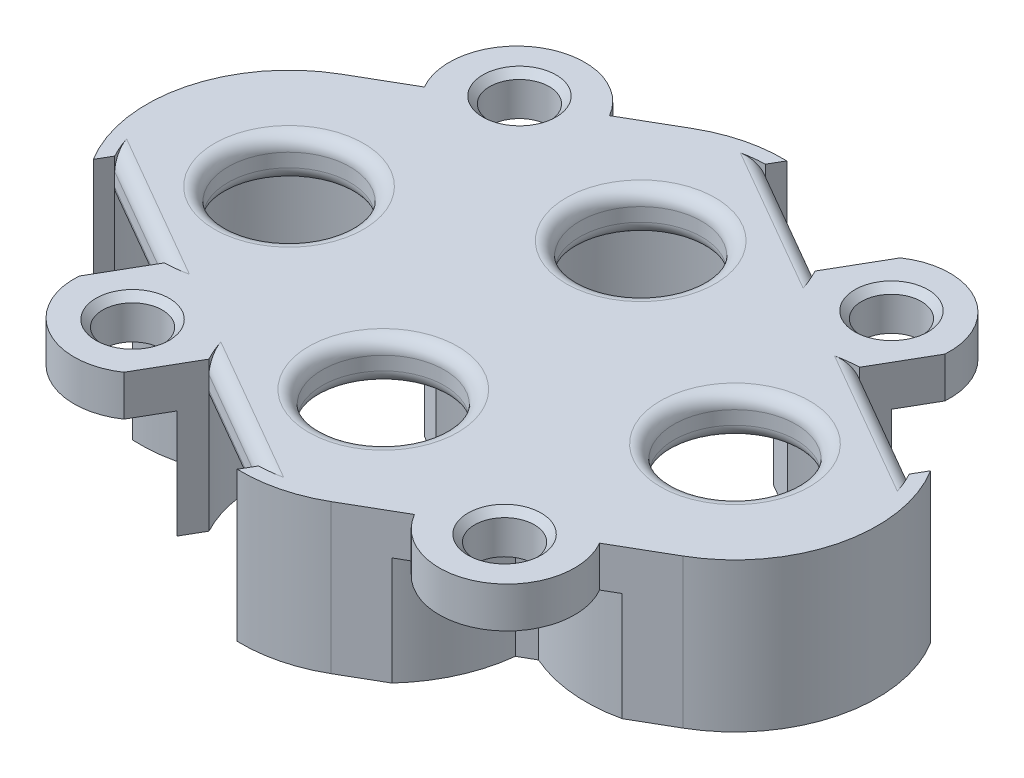
SolidWorks part; units mm, degrees
note: The reader was unsure of these and kept them because the rebuilt part matched: shared geometry of "Sketch1<4>", "Sketch1<6>".
ref_plane "Front Plane" through (0, 0, 0) normal (0, 0, 1) x (1, 0, 0)
ref_plane "Top Plane" through (0, 0, 0) normal (0, 1, 0) x (1, 0, 0)
ref_plane "Right Plane" through (0, 0, 0) normal (1, 0, 0) x (0, 0, -1)
sketch "Sketch1" plane through (0, 0, 0) normal (0, 1, 0) x (1, 0, 0)
  line L0 (-11.9589, 8.369) -> (-9.4955, 9.7913)
  line L1 (-6.9589, -0.2913) -> (-4.4955, 1.131)
  line L2 (-16.4545, 0) -> (0, 9.5) construction
  line L3 (-12.0193, 10.0662) -> (-10.9352, 10.6921)
  line L4 (0, 9.0625) -> (0, -9.0625) construction
  line L5 (-16.4545, 0) -> (16.4545, 0) construction
  line L6 (-5.25, 18.5933) -> (-21.7045, 9.0933)
  line L7 (5.25, -18.5933) -> (21.7045, -9.0933)
  line L8 (-21.7045, -9.0933) -> (-5.25, -18.5933)
  line L9 (5.25, 18.5933) -> (21.7045, 9.0933)
  line L10 (-12.0193, -10.0662) -> (-10.9352, -10.6921)
  line L11 (-16.4545, 0) -> (0, -9.5) construction
  line L12 (0, -19) -> (0, -20)
  line L13 (0, 20) -> (0, 19)
  line L14 (-11.9589, -8.369) -> (-9.4955, -9.7913)
  line L15 (0, 0) -> (-27.9836, 16.1563) construction
  circle A0 centre (-16.4545, 0) radius 9.5
  circle A1 centre (0, 9.5) radius 9.5
  circle A2 centre (16.4545, 0) radius 9.5
  circle A3 centre (0, -9.5) radius 9.5
  arc A4 (-21.7045, 9.0933) -> (-21.7045, -9.0933) centre (-16.4545, 0) ccw
  arc A5 (-5.25, -18.5933) -> (5.25, -18.5933) centre (0, -9.5) ccw
  arc A6 (21.7045, 9.0933) -> (21.7045, -9.0933) centre (16.4545, 0) cw
  arc A7 (-5.25, 18.5933) -> (5.25, 18.5933) centre (0, 9.5) cw
  arc A8 (-18.865, -10.7326) -> (-10.9999, -9.5523) centre (-16.4545, 0) ccw
  arc A9 (-8.0895, 16.9539) -> (-10.9999, 9.5523) centre (0, 9.5) ccw
  circle A12 centre (0, 9.5) radius 11 construction
  circle A13 centre (-16.4545, 0) radius 11 construction
  arc A15 (-10.9999, -9.5523) -> (-8.0895, -16.9539) centre (0, -9.5) ccw
  arc A19 (-10.9999, 9.5523) -> (-18.865, 10.7326) centre (-16.4545, 0) ccw
  dimension "D1" = 19
  dimension "D2" = 19
  dimension "D3" = 19
  dimension "D4" = 19
  dimension "D5" = 10.5
  dimension "D6" = 10.5
  dimension "D7" = 10.5
  dimension "D8" = 10.5
  dimension "D9" = 11
  dimension "D11" = 11
  dimension "D13" = 5
  dimension "D14" = 5
  dimension "D15" = 1.5
  dimension "D16" = 6.5
  dimension "D17" = 5
  dimension "D10" = 1.5
extrude "Boss-Extrude1" add sketch "Sketch1" against normal blind 3
extrude "Boss-Extrude2" add sketch "Sketch1<4>" against normal blind 3 contours A1 | A3
sketch "Sketch1<4>" plane through (0, 0, 0) normal (0, 1, 0) x (1, 0, 0) same geometry as "Sketch1"
extrude "Boss-Extrude3" add sketch "Sketch1<6>" along normal blind 8 and the other way offset from surface (11 mm away) 8
sketch "Sketch1<6>" plane through (0, 0, 0) normal (0, 1, 0) x (1, 0, 0) same geometry as "Sketch1"
sketch "Sketch3" plane through (0, 0, 0) normal (0, 1, 0) x (1, 0, 0)
  line L2 (-18.865, -10.7326) -> (-8.0895, -16.9539) construction
  line L3 (-8.0895, 16.9539) -> (-18.865, 10.7326) construction
  line L5 (-17.8074, -11.3433) -> (-9.1471, -16.3433)
  line L6 (-17.8074, 11.3433) -> (-9.1471, 16.3433)
  line L7 (-10.9999, -9.5523) -> (-12.1217, -11.4953) construction
  line L8 (-16.4545, 0) -> (0, -9.5) construction
  line L9 (-12.0193, -10.0662) -> (-10.9352, -10.6921) construction
  line L10 (-10.9999, 9.5523) -> (-11.9287, 11.1612) construction
  line L11 (-16.4545, 0) -> (0, 9.5) construction
  line L12 (-12.0193, 10.0662) -> (-10.9352, 10.6921) construction
  arc A0 (-17.8074, -11.3433) -> (-9.1471, -16.3433) centre (-13.4772, -13.8433) ccw
  arc A1 (-17.8074, 11.3433) -> (-9.1471, 16.3433) centre (-13.4772, 13.8433) cw
  dimension "D1" = 4
  dimension "D2" = 5
  dimension "D4" = 5
  dimension "D3" = 4
extrude "Boss-Extrude4" add sketch "Sketch3" against normal blind 3
sketch "Sketch4" plane through (0, 0, 0) normal (0, 1, 0) x (1, 0, 0)
  line L0 (-11.4772, -10.3792) -> (-13.7272, -14.2763)
  line L1 (-12.0193, -10.0662) -> (-10.9352, -10.6921) construction
  line L2 (-12.0193, -10.0662) -> (-10.9352, -10.6921) construction
  line L3 (-13.7272, 14.2763) -> (-11.4772, 10.3792)
  line L4 (-12.0193, 10.0662) -> (-10.9352, 10.6921) construction
  circle A0 centre (-13.7272, -14.2763) radius 2.2
  circle A1 centre (-13.7272, 14.2763) radius 2.2
  dimension "D1" = 4.4
  dimension "D3" = 4.4
  dimension "D2" = 4.5
  dimension "D4" = 4.5
extrude "Cut-Extrude1" cut sketch "Sketch4" against normal up to next
chamfer "Chamfer1" distance 0.5 angle 45 2 edges at (-13.7272, 0, 16.4763) (-13.7272, 0, -12.0763)
mirror "Mirror1" about plane through (0, 0, 0) normal (1, 0, 0) of "Chamfer1", "Cut-Extrude1", "Boss-Extrude3", "Boss-Extrude4"
sketch "Sketch5" plane through (0, 8, 0) normal (0, 1, 0) x (1, 0, 0)
  line L0 (-17.6743, 0) -> (16.6223, 0) construction
  line L1 (0, 0) -> (0, -9.5473) construction
  line L2 (-16.4545, 0) -> (0, -9.5) construction
  line L3 (-16.4545, 0) -> (-23.6771, -12.5099) construction
  line L4 (0, -9.5) -> (-7.4901, -22.4732) construction
  line L5 (-24.8235, -4.4955) -> (-16.1632, -9.4955)
  line L6 (-24.8235, -4.4955) -> (-27.1243, -8.4807)
  line L7 (-16.1632, -9.4955) -> (-18.4641, -13.4807)
  line L8 (-27.1243, -8.4807) -> (-18.4641, -13.4807)
  line L9 (-8.369, -13.9955) -> (0.2913, -18.9955)
  line L10 (-8.369, -13.9955) -> (-10.6699, -17.9807)
  line L11 (0.2913, -18.9955) -> (-2.0096, -22.9807)
  line L12 (-10.6699, -17.9807) -> (-2.0096, -22.9807)
  line L15 (16.4545, 0) -> (21.7045, 9.0933) construction
  line L16 (0, 9.5) -> (5.25, 18.5933) construction
  line L17 (-0.2913, 18.9955) -> (8.369, 13.9955)
  line L18 (-0.2913, 18.9955) -> (2.0096, 22.9807)
  line L19 (8.369, 13.9955) -> (10.6699, 17.9807)
  line L20 (2.0096, 22.9807) -> (10.6699, 17.9807)
  line L21 (16.1632, 9.4955) -> (24.8235, 4.4955)
  line L22 (16.1632, 9.4955) -> (18.4641, 13.4807)
  line L23 (24.8235, 4.4955) -> (27.1243, 8.4807)
  line L24 (18.4641, 13.4807) -> (27.1243, 8.4807)
  arc A0 (-11.9589, 8.369) -> (-11.9589, -8.369) centre (-16.4545, 0) ccw construction
  arc A1 (-9.4955, -9.7913) -> (9.4955, -9.7913) centre (0, -9.5) ccw construction
  arc A2 (11.9589, -8.369) -> (11.9589, 8.369) centre (16.4545, 0) ccw construction
  arc A3 (-17.8074, -11.3433) -> (-9.1471, -16.3433) centre (-13.4772, -13.8433) ccw construction
  arc A4 (-9.4955, -9.7913) -> (9.4955, -9.7913) centre (0, -9.5) ccw construction
  arc A5 (17.8074, 11.3433) -> (9.1471, 16.3433) centre (13.4772, 13.8433) ccw construction
  circle A7 centre (0, 9.5) radius 9.5 construction
  point P1 (-16.4545, 0)
  point P9 (0, -9.5)
  dimension "D1" = 10
  dimension "D3" = 5
  dimension "D4" = 5
  dimension "D5" = 10
  dimension "D8" = 10
  dimension "D9" = 5
  dimension "D11" = 10
  dimension "D12" = 5
extrude "Cut-Extrude2" cut sketch "Sketch5" against normal up to next
fillet "Fillet1" radius 1 8 edges at (-20.4934, 0, 6.9955) (-20.4934, -3, 6.9955) (-4.0389, 0, 16.4955) (-4.0389, -3, 16.4955) (4.0389, 0, -16.4955) (4.0389, -3, -16.4955) (20.4934, 0, -6.9955) (20.4934, -3, -6.9955)
sketch "Sketch6" plane through (0, 0, 0) normal (0, 1, 0) x (1, 0, 0)
  line L8 (-16.4545, 0) -> (0, 9.5) construction
  line L11 (-6.9589, 0.2913) -> (-4.4955, -1.131)
  line L12 (-16.4545, 0) -> (0, -9.5) construction
  line L13 (-4.4955, 1.131) -> (-6.9589, -0.2913)
  line L14 (-2, 0.2129) -> (-2, -0.2129)
  line L15 (-16.4545, 0) -> (16.4545, 0) construction
  line L16 (4.4955, 1.131) -> (6.9589, -0.2913)
  line L17 (0, 9.5) -> (16.4545, 0) construction
  line L18 (173205.0808, -100000) -> (-173233.0643, 100016.1563) construction
  line L19 (2, 0.2129) -> (2, -0.2129)
  line L20 (6.9589, 0.2913) -> (4.4955, -1.131)
  arc A2 (-8.2272, 4.75) -> (0, 0) centre (0, 9.5) ccw
  circle A16 centre (0, 9.5) radius 9.5 construction
  circle A24 centre (-16.4545, 0) radius 9.5 construction
  circle A25 centre (0, -9.5) radius 9.5 construction
  arc A26 (-6.9589, 0.2913) -> (-8.2272, 4.75) centre (-16.4545, 0) ccw
  arc A27 (0, 0) -> (-4.4955, -1.131) centre (0, -9.5) ccw
  circle A28 centre (16.4545, 0) radius 9.5 construction
  arc A29 (4.4955, 1.131) -> (0, 0) centre (0, 9.5) cw
  arc A30 (8.2272, -4.75) -> (6.9589, -0.2913) centre (16.4545, 0) cw
  arc A31 (8.2272, -4.75) -> (0, 0) centre (0, -9.5) ccw
  dimension "D1" = 5
  dimension "D2" = 2
  dimension "D3" = 5
  dimension "D4" = 10
  dimension "D5" = 2
  dimension "D6" = 5
extrude "Boss-Extrude5" add sketch "Sketch6" along normal blind 8 and the other way offset from surface (11 mm away) 8 contours A27 L14 A2 L13 A26 L11 | A31 L20 A30 L16 A29 L19
sketch "Sketch7" plane through (0, 0, 0) normal (0, 0, 1) x (1, 0, 0)
  line L0 (-26.9545, 8) -> (-26.9545, -11) construction
  line L1 (-26.9545, 0) -> (26.9545, 0)
  line L2 (-26.9545, 0) -> (-26.9545, 8)
  line L3 (-26.9545, 8) -> (26.9545, 8)
  line L4 (26.9545, 0) -> (26.9545, 8)
  line L5 (-11.9589, 0) -> (-25.9545, 0) construction
extrude "Cut-Extrude3" cut sketch "Sketch7" against normal through all both and the other way through all
sketch "Sketch8" plane through (0, -3, 0) normal (0, -1, 0) x (1, 0, 0)
  circle A0 centre (-16.4545, 0) radius 4.5
  circle A1 centre (0, 9.5) radius 4.5
  circle A2 centre (16.4545, 0) radius 4.5
  circle A3 centre (0, -9.5) radius 4.5
  arc A4 (-25.4812, 2.9611) -> (-11.9589, -8.369) centre (-16.4545, 0) ccw construction
  arc A5 (9.4955, 9.7913) -> (0.2913, 18.9955) centre (0, 9.5) ccw construction
  arc A6 (-9.4955, -9.7913) -> (-1.949, -18.7979) centre (0, -9.5) ccw construction
  arc A7 (25.4812, -2.9611) -> (11.9589, 8.369) centre (16.4545, 0) ccw construction
  dimension "D1" = 9
  dimension "D2" = 9
  dimension "D3" = 9
  dimension "D4" = 9
extrude "Cut-Extrude4" cut sketch "Sketch8" against normal up to next
fillet "Fillet2" radius 1 8 edges at (16.4545, 0, 4.5) (16.4545, -3, -4.5) (0, 0, 14) (0, -3, 5) (0, 0, -5) (0, -3, -14) (-16.4545, 0, 4.5) (-16.4545, -3, -4.5)
equation "\"D2@Sketch1\"=\"D1@Sketch1\""
equation "\"D3@Sketch1\"=\"D1@Sketch1\""
equation "\"D4@Sketch1\"=\"D1@Sketch1\""
equation "\"D2@Sketch8\"=\"D1@Sketch8\""
equation "\"D3@Sketch8\"=\"D1@Sketch8\""
equation "\"D4@Sketch8\"=\"D1@Sketch8\""
